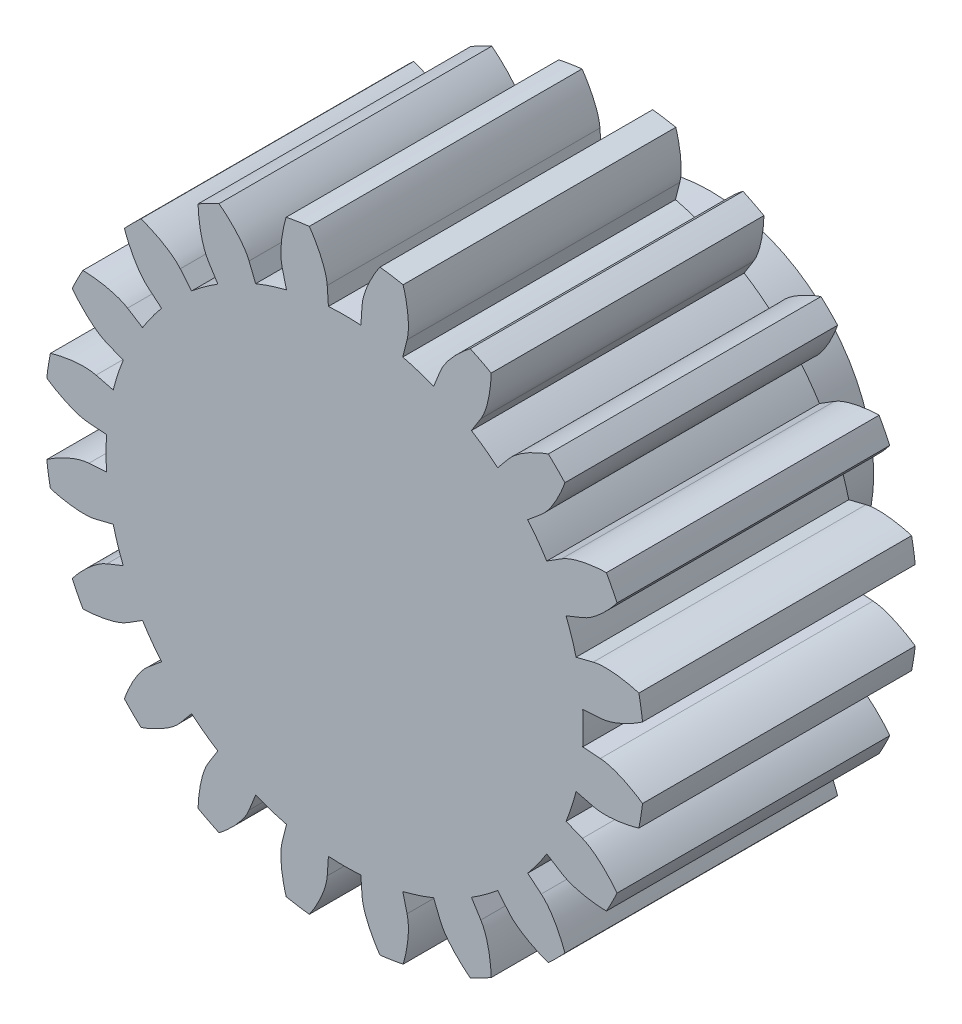
SolidWorks part; units mm, degrees
ref_plane "前视基准面" through (0, 0, 0) normal (0, 0, 1) x (1, 0, 0)
ref_plane "上视基准面" through (0, 0, 0) normal (0, 1, 0) x (1, 0, 0)
ref_plane "右视基准面" through (0, 0, 0) normal (1, 0, 0) x (0, 0, -1)
other "Configuration Table"
sketch "草图1" plane through (0, 0, 0) normal (0, 0, 1) x (1, 0, 0)
  line L0 (0, 0) -> (5, 0) construction
  line L1 (0, 0) -> (4.9846, 0.3923) construction
  line L2 (0, 0) -> (4.6876, 0.3194)
  line L3 (4.9846, 0.3923) -> (4.9846, -0.3923) construction
  line L4 (0, 0) -> (4.6876, -0.3194)
  circle A0 centre (0, 0) radius 5.5
  circle A1 centre (0, 0) radius 5 construction
  circle A2 centre (0, 0) radius 4.375
  circle A3 centre (0, 0) radius 4.6985 construction
  circle A4 centre (0, 0) radius 1.475
  spline S0 degree 4 poles (4.6876, 0.3194) (4.7233, 0.3218) (4.8225, 0.336) (5.0062, 0.3926) (5.2885, 0.5242) (5.6241, 0.7499) (6.0094, 1.0976) (6.395, 1.5688) (6.7398, 2.1414) (7.0933, 2.9696) (7.3065, 3.8467) (7.3947, 4.7795) (7.347, 5.8934) (7.1568, 6.9938) (6.7515, 8.227) (6.0949, 9.5107) (5.2611, 10.6861) (4.2765, 11.7378) (3.1662, 12.6551) (1.9531, 13.4307) (0.6586, 14.0604) (-0.5283, 14.4821) (-1.4854, 14.7287) (-2.1912, 14.8654) (-2.6338, 14.9356) (-2.9917, 14.9827) (-3.3451, 15.0208) (-3.7095, 15.05) (-4.0266, 15.0684) (-4.3306, 15.0786) (-4.6986, 15.0842) (-4.9527, 15.0816) (-5.4001, 15.0704) (-5.6957, 15.0494) (-6.0237, 15.027) (-6.2862, 14.9991) (-6.5922, 14.9657) (-6.7961, 14.9366) (-6.9439, 14.9154) (-7.0152, 14.9043) knots 0 0 0 0 0 0.005604 0.015718 0.02996 0.048734 0.068727 0.096889 0.125051 0.153212 0.209535 0.237696 0.271429 0.327752 0.384075 0.440398 0.496721 0.553044 0.609367 0.66569 0.722013 0.778336 0.806497 0.820578 0.834659 0.84874 0.86282 0.876901 0.890982 0.900036 0.909091 0.931818 0.943182 0.954545 0.965909 0.977273 0.988636 1 1 1 1 1 construction
  spline S1 degree 4 poles (4.6876, 0.3194) (4.7233, 0.3218) (4.8225, 0.336) (5.0062, 0.3926) (5.2885, 0.5242) (5.6241, 0.7499) (6.0094, 1.0976) (6.395, 1.5688) (6.7398, 2.1414) (7.0933, 2.9696) (7.3065, 3.8467) (7.3947, 4.7795) (7.347, 5.8934) (7.1568, 6.9938) (6.7515, 8.227) (6.0949, 9.5107) (5.2611, 10.6861) (4.2765, 11.7378) (3.1662, 12.6551) (1.9531, 13.4307) (0.6586, 14.0604) (-0.5283, 14.4821) (-1.4854, 14.7287) (-2.1912, 14.8654) (-2.6338, 14.9356) (-2.9917, 14.9827) (-3.3451, 15.0208) (-3.7095, 15.05) (-4.0266, 15.0684) (-4.3306, 15.0786) (-4.5463, 15.0819) (-4.6529, 15.0825) (-4.7054, 15.0825) knots 0 0 0 0 0 0.005604 0.015718 0.02996 0.048734 0.068727 0.096889 0.125051 0.153212 0.209535 0.237696 0.271429 0.327752 0.384075 0.440398 0.496721 0.553044 0.609367 0.66569 0.722013 0.778336 0.806497 0.820578 0.834659 0.84874 0.86282 0.876901 0.890982 0.900036 0.909091 0.909091 0.909091 0.909091 0.909091
  spline S2 degree 4 poles (4.6876, -0.3194) (4.7233, -0.3218) (4.8225, -0.336) (5.0062, -0.3926) (5.2885, -0.5242) (5.6241, -0.7499) (6.0094, -1.0976) (6.395, -1.5688) (6.7398, -2.1414) (7.0933, -2.9696) (7.3065, -3.8467) (7.3947, -4.7795) (7.347, -5.8934) (7.1568, -6.9938) (6.7515, -8.227) (6.0949, -9.5107) (5.2611, -10.6861) (4.2765, -11.7378) (3.1662, -12.6551) (1.9531, -13.4307) (0.6586, -14.0604) (-0.5283, -14.4821) (-1.4854, -14.7287) (-2.1912, -14.8654) (-2.6338, -14.9356) (-2.9917, -14.9827) (-3.3451, -15.0208) (-3.7095, -15.05) (-4.0266, -15.0684) (-4.3306, -15.0786) (-4.6986, -15.0842) (-4.9527, -15.0816) (-5.4001, -15.0704) (-5.6957, -15.0494) (-6.0237, -15.027) (-6.2862, -14.9991) (-6.5922, -14.9657) (-6.7961, -14.9366) (-6.9439, -14.9154) (-7.0152, -14.9043) knots 0 0 0 0 0 0.005604 0.015718 0.02996 0.048734 0.068727 0.096889 0.125051 0.153212 0.209535 0.237696 0.271429 0.327752 0.384075 0.440398 0.496721 0.553044 0.609367 0.66569 0.722013 0.778336 0.806497 0.820578 0.834659 0.84874 0.86282 0.876901 0.890982 0.900036 0.909091 0.931818 0.943182 0.954545 0.965909 0.977273 0.988636 1 1 1 1 1 construction
  spline S3 degree 4 poles (4.6876, -0.3194) (4.7233, -0.3218) (4.8225, -0.336) (5.0062, -0.3926) (5.2885, -0.5242) (5.6241, -0.7499) (6.0094, -1.0976) (6.395, -1.5688) (6.7398, -2.1414) (7.0933, -2.9696) (7.3065, -3.8467) (7.3947, -4.7795) (7.347, -5.8934) (7.1568, -6.9938) (6.7515, -8.227) (6.0949, -9.5107) (5.2611, -10.6861) (4.2765, -11.7378) (3.1662, -12.6551) (1.9531, -13.4307) (0.6586, -14.0604) (-0.5283, -14.4821) (-1.4854, -14.7287) (-2.1912, -14.8654) (-2.6338, -14.9356) (-2.9917, -14.9827) (-3.3451, -15.0208) (-3.7095, -15.05) (-4.0266, -15.0684) (-4.3306, -15.0786) (-4.5463, -15.0819) (-4.6529, -15.0825) (-4.7054, -15.0825) knots 0 0 0 0 0 0.005604 0.015718 0.02996 0.048734 0.068727 0.096889 0.125051 0.153212 0.209535 0.237696 0.271429 0.327752 0.384075 0.440398 0.496721 0.553044 0.609367 0.66569 0.722013 0.778336 0.806497 0.820578 0.834659 0.84874 0.86282 0.876901 0.890982 0.900036 0.909091 0.909091 0.909091 0.909091 0.909091
  point P15 (4.9846, 0)
  dimension "齿顶圆直径" = 11
  dimension "分度圆直径" = 10
  dimension "齿根圆直径" = 8.75
  dimension "基圆直径" = 9.3969
  dimension "内孔直径" = 2.95
  dimension "渐近线镜像线夹角" = 4.5
extrude "凸台-拉伸1" add sketch "草图1" along normal blind 5 contours A0 | A4
extrude "切除-拉伸1" cut sketch "草图1<3>" along normal through all contours A2 S3 A0 S1 region at (5.0102, 0, 0)
sketch "草图1<3>" plane through (0, 0, 0) normal (0, 0, 1) x (1, 0, 0) same geometry as "草图1"
pattern_circular "阵列(圆周)1" count 20 every 18 about axis through (0, 0, 5) along (0, 0, 1) of "切除-拉伸1"
sketch "草图2" plane through (0, 0, 5) normal (0, 0, 1) x (1, 0, 0)
  circle A0 centre (0, 0) radius 1.475
extrude "凸台-拉伸2" add sketch "草图2" against normal through all
sketch "草图3" plane through (0, 0, 0) normal (0, 0, -1) x (-1, 0, 0)
  line L7 (-1, 0.25) -> (1, 0.25)
  line L8 (-1, 0.25) -> (-1, -0.25)
  line L9 (-1, -0.25) -> (1, -0.25)
  line L10 (1, 0.25) -> (1, -0.25)
  line L11 (-0.25, 1) -> (0.25, 1)
  line L12 (-0.25, 1) -> (-0.25, -1)
  line L13 (-0.25, -1) -> (0.25, -1)
  line L14 (0.25, 1) -> (0.25, -1)
  circle A0 centre (0, 0) radius 2
  circle A1 centre (0, 0) radius 3
  point P12 (0, 0)
  point P13 (0, 1)
  point P14 (-0.25, 0)
  point P15 (-1, 0)
  point P16 (0, 0.25)
  dimension "D1" = 1
  dimension "D2" = 4
  dimension "D3" = 2
  dimension "D4" = 0.5
extrude "凸台-拉伸3" add sketch "草图3" along normal blind 1.7 contours A1 A0 | L9 L10 L7 L8 | L12 L13 L14 L11 region at (2.9151, 0, 0)
sketch "草图4" plane through (0, 0, 5) normal (0, 0, 1) x (1, 0, 0)
  line L0 (1, 1.118) -> (1, -1.118)
  circle A0 centre (0, 0) radius 1.5
  dimension "D1" = 3
  dimension "D2" = 1
sketch "草图5" plane through (0, 0, -1.7) normal (0, 0, -1) x (-1, 0, 0)
  circle A0 centre (0, 0) radius 2
  circle A1 centre (0, 0) radius 2 construction
extrude "切除-拉伸2" cut sketch "草图5" against normal blind 1
equation "\"m\"= 0.5'模数"
equation "\"z\"= 20'齿数"
equation "\"a\"= 20度'压力角"
equation "\"d\"= \"m\" * \"z\"'分度圆直径"
equation "\"da\"= ( \"z\" + 2 ) * \"m\"'齿顶圆直径"
equation "\"df\"= ( \"z\" - 2.5 ) * \"m\"'齿根圆直径"
equation "\"s\"= 0.5 * PI * \"m\"'分度圆齿厚"
equation "\"r\"= 0.38 * \"m\"'齿根圆角"
equation "\"B\"= 0.3 * \"d\"'齿厚"
equation "\"db\"= \"m\" * \"z\" * cos ( \"a\" )'基圆直径"
equation "\"rb\"= \"db\" / 2'基圆半径"
equation "\"齿顶圆直径@草图1\"= \"da\""
equation "\"分度圆直径@草图1\"= \"d\""
equation "\"齿根圆直径@草图1\"= \"df\""
equation "\"基圆直径@草图1\"= \"db\""
equation "\"渐近线镜像线夹角@草图1\"= 360 / 4 / \"z\""
equation "\"h\"= 5'齿轮厚度"
equation "\"ir\"= 2.95'内孔直径"
equation "\"内孔直径@草图1\"= \"ir\""
equation "\"齿轮厚@凸台-拉伸1\"= \"h\""
equation "\"齿轮夹角@阵列(圆周)1\"= 360 / \"z\""
equation "\"齿数@阵列(圆周)1\"= \"z\""
